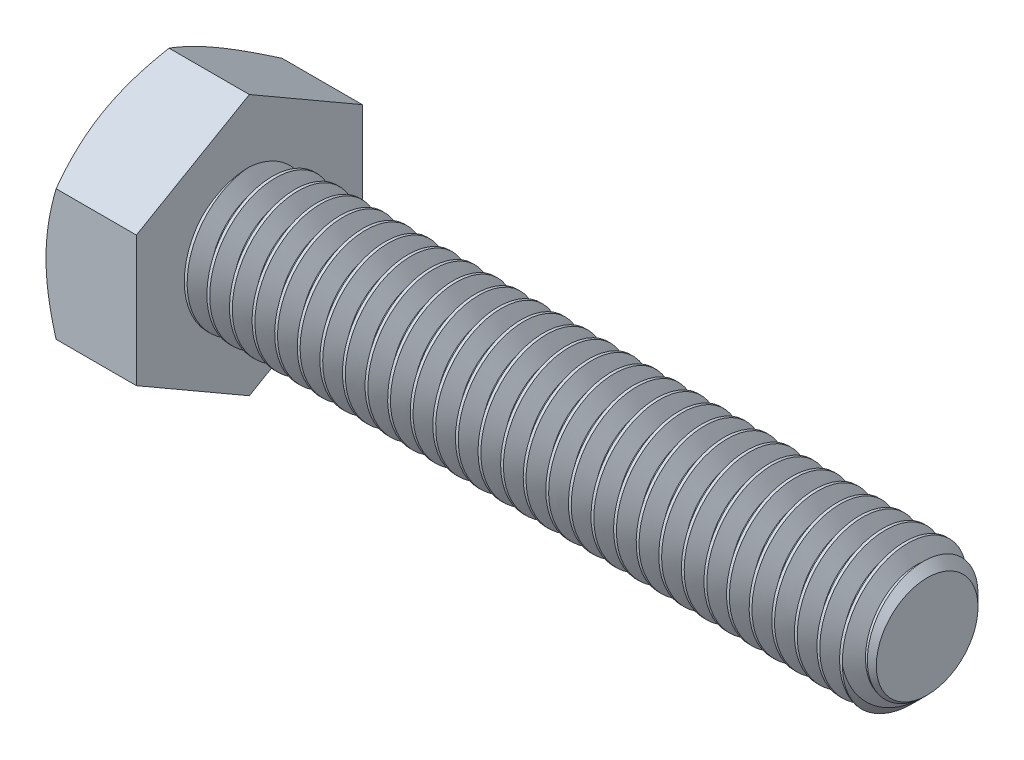
SolidWorks part; units mm, degrees
ref_plane "Front Plane" through (0, 0, 0) normal (0, 0, 1) x (1, 0, 0)
ref_plane "Top Plane" through (0, 0, 0) normal (0, 1, 0) x (1, 0, 0)
ref_plane "Right Plane" through (0, 0, 0) normal (1, 0, 0) x (0, 0, -1)
sketch "Sketch1" plane through (0, 0, 0) normal (0, 0, 1) x (1, 0, 0)
  line L0 (-17, 0) -> (17, 0) construction
  line L1 (-13, 5) -> (-13, -5) construction
  line L2 (-17, 5) -> (-17, -5) construction
  line L3 (17, 3) -> (17, -3) construction
  point P8 (13.5, -3)
  dimension "D1" = 3.5
  dimension "Thread Dia" = 6
  dimension "Hex" = 10
  dimension "Head Ht" = 4
  dimension "Length" = 30
ref_plane "Plane2" through (17, 0, 0) normal (1, 0, 0) x (0, 0, -1)
sketch "Sketch2" plane through (17, 0, 0) normal (1, 0, 0) x (0, 0, -1)
  circle A0 centre (0, 0) radius 3
extrude "Boss-Extrude1" add sketch "Sketch2" against normal up to vertex (30 mm away) up to point (-13, -5, 0)
sketch "Sketch4" plane through (17, 0, 0) normal (1, 0, 0) x (0, 0, -1)
  circle A1 centre (0, 0) radius 3
  circle A2 centre (0, 0) radius 3
  dimension "D1" = 0
curve "Helix/Spiral1" pitch 1 height 31 turns 31 parameters "Pitch"=1
chamfer "Chamfer1" distance 0.75 angle 45 1 edges at (17, 0, -3)
sketch "Sketch5" plane through (0, 0, 0) normal (0, 0, 1) x (1, 0, 0)
  line L0 (17, 3) -> (17.375, 2.3505)
  line L1 (17.375, 2.3505) -> (17.5, 2.3505)
  line L2 (17.5, 2.3505) -> (17.875, 3)
  line L3 (17, 3) -> (17.875, 3)
  line L4 (17.4375, 2.3505) -> (17.4375, 3) construction
  line L5 (17.1875, 2.6752) -> (17.6875, 2.6752) construction
  line L6 (17, -3) -> (17, 3) construction
  dimension "D1" = 60
  dimension "D2" = 0.125
  dimension "D3" = 0.5
sweep "Cut-Sweep1" cut profiles "Sketch5" path "Helix/Spiral1"
sketch "Sketch3" plane through (-13, 0, 0) normal (-1, 0, 0) x (0, 0, 1)
  line L0 (0, 5) -> (0, -5) construction
  line L1 (-5, -2.8868) -> (0, -5.7735)
  line L2 (0, -5.7735) -> (5, -2.8868)
  line L3 (5, -2.8868) -> (5, 2.8868)
  line L4 (5, 2.8868) -> (0, 5.7735)
  line L5 (0, 5.7735) -> (-5, 2.8868)
  line L6 (-5, 2.8868) -> (-5, -2.8868)
  circle A0 centre (0, 0) radius 5 construction
extrude "Boss-Extrude2" add sketch "Sketch3" along normal up to vertex (4 mm away) up to point (-17, -5, 0)
sketch "Sketch6" plane through (-17, 0, 0) normal (-1, 0, 0) x (0, 0, 1)
  circle A0 centre (0, 0) radius 5 construction
  circle A1 centre (0, 0) radius 5
extrude "Cut-Extrude1" cut sketch "Sketch6" against normal through all draft 60 flip side to cut
sketch "Sketch7" plane through (-17, 0, 0) normal (-1, 0, 0) x (0, 0, 1)
  line L0 (0, 0) -> (0, 5) construction
  line L2 (0, 5) -> (0, -5) construction
  line L3 (-4.3301, 2.5) -> (4.3301, 2.5) construction
  circle A1 centre (0, 0) radius 5 construction
  text T0 "8.8\r\n" font "Arial" height in points 6
  point P8 (0, 2.5)
extrude "Cut-Extrude2" cut sketch "Sketch7" against normal blind 0.25
sketch "Sketch9" plane through (0, 0, 0) normal (0, 0, 1) x (1, 0, 0)
  line L0 (-13, 3) -> (-13, 0)
  line L1 (-13, 0) -> (-34, 0)
  line L2 (-34, 0) -> (-37, 3)
  line L3 (-37, 3) -> (-13, 3)
  line L4 (-17, 0) -> (17, 0) construction
  line L5 (-13, 5) -> (-13, -5) construction
  line L6 (17, 3) -> (17, -3) construction
  dimension "D1" = 45
  dimension "MinThreadLg" = 54
revolve "Revolve1" [suppressed] add sketch "Sketch9" angle 360 about L1
equation "\"D2@Sketch5\" = \"Pitch@Helix/Spiral1\"*.125"
equation "\"D3@Sketch5\" = \"Pitch@Helix/Spiral1\"*.50"
equation "\"D3@Helix/Spiral1\" = \"Length@Sketch1\"+\"Pitch@Helix/Spiral1\""
equation "\"D1@Chamfer1\" = \"Pitch@Helix/Spiral1\"*.750"
equation "\"D1@Sketch1\" = \"Pitch@Helix/Spiral1\"*3.50"
